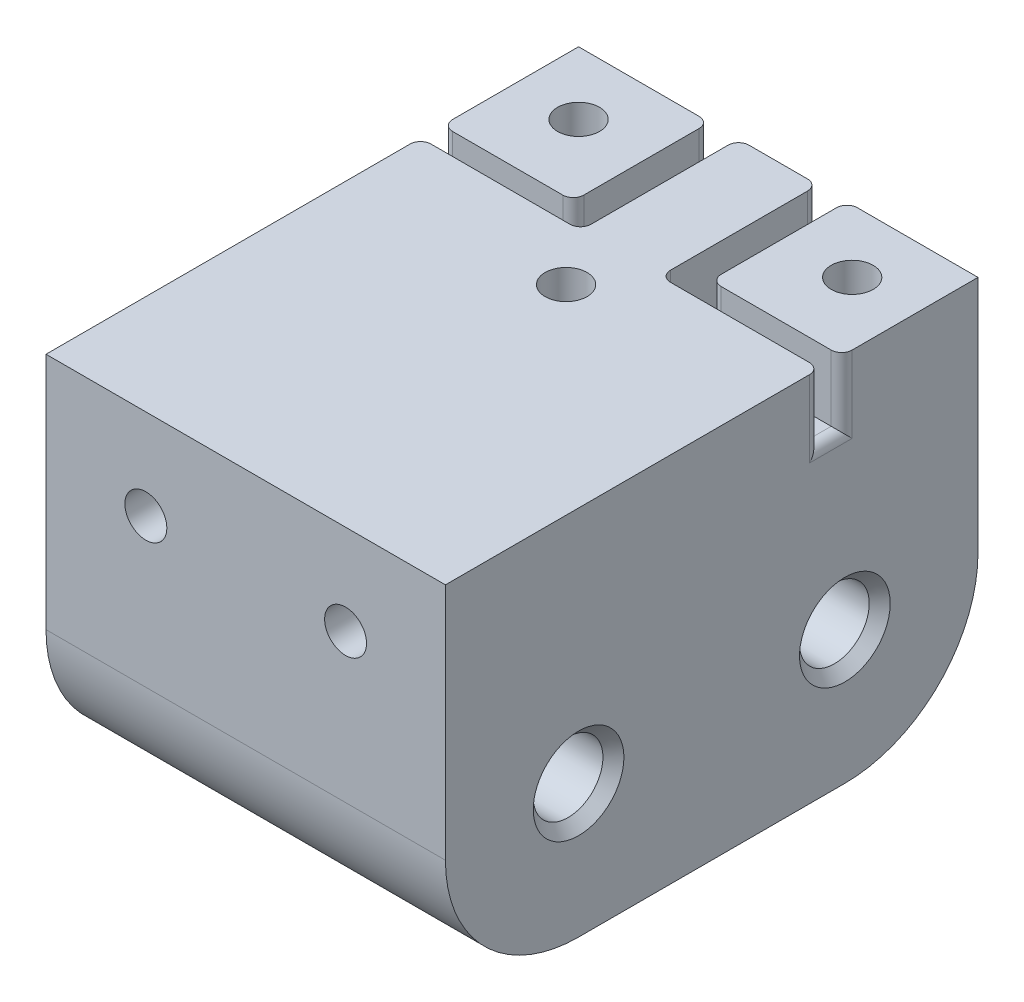
SolidWorks part; units mm, degrees
ref_plane "Front Plane" through (0, 0, 0) normal (0, 0, 1) x (1, 0, 0)
ref_plane "Top Plane" through (0, 0, 0) normal (0, 1, 0) x (1, 0, 0)
ref_plane "Right Plane" through (0, 0, 0) normal (1, 0, 0) x (0, 0, -1)
sketch "Sketch1" plane through (0, 0, 0) normal (1, 0, 0) x (0, 0, -1)
  line L0 (25.4, 22.75) -> (25.4, 0) construction
  line L1 (0, 22.75) -> (50.8, 22.75)
  line L2 (0, 22.75) -> (0, 0)
  line L3 (0, 0) -> (50.8, 0)
  line L4 (50.8, 22.75) -> (50.8, 0)
  circle A0 centre (12.7, 0) radius 3.325
  circle A1 centre (38.1, 0) radius 3.325
  circle A2 centre (12.7, 0) radius 12.7
  circle A3 centre (38.1, 0) radius 12.7
  dimension "D1" = 6.65
  dimension "D6" = 25.4
  dimension "D2" = 25.4
  dimension "D3" = 50.8
  dimension "D4" = 12.7
  dimension "D5" = 22.75
extrude "Boss-Extrude2" add sketch "Sketch1" along normal blind 38.1 contours L3 A2 A0 | L3 A2 A0 | L3 A3 A1 | L3 A3 A1 | L1 L0 L3 A3 L4 | L0 L1 L2 L3 A2 region at (0, 16.0478, -38.1) region at (0, 16.0478, -12.7) region at (0, -5.6828, -12.7) region at (0, 5.6828, -38.1) region at (0, 5.6828, -12.7) region at (0, -5.6828, -38.1)
ref_plane "Plane1" through (0, -12.7, 0) normal (0, -1, 0) x (-1, 0, 0)
sketch "Sketch6" plane through (0, -12.7, 0) normal (0, -1, 0) x (-1, 0, 0)
  line L0 (-38.1, 38.1) -> (0, 38.1)
  line L1 (-38.1, 50.8) -> (-38.1, 25.4) construction
  line L2 (0, 25.4) -> (0, 50.8) construction
  line L3 (-38.1, 12.7) -> (0, 12.7)
  line L4 (-38.1, 25.4) -> (-38.1, 0) construction
  line L5 (0, 0) -> (0, 25.4) construction
  line L7 (-38.1, 38.1) -> (0, 38.1)
  line L8 (-38.1, 38.1) -> (-38.1, 12.7)
  line L9 (-38.1, 12.7) -> (0, 12.7)
  line L10 (0, 38.1) -> (0, 12.7)
  circle A0 centre (-19.05, 38.1) radius 2
  circle A1 centre (-19.05, 12.7) radius 2
  dimension "D1" = 4
extrude "Cut-Extrude5" cut sketch "Sketch6" against normal up to next contours A0 | A1
extrude "Boss-Extrude3" add sketch "Sketch6<3>" against normal up to next contours A1 L3 L10 L0 A0 L8 region at (19.05, -12.7, -25.4)
sketch "Sketch6<3>" plane through (0, -12.7, 0) normal (0, -1, 0) x (-1, 0, 0) same geometry as "Sketch6"
sketch "Sketch10" plane through (0, 0, 0) normal (0, 0, 1) x (1, 0, 0)
  line L0 (38.1, 22.75) -> (38.1, 0) construction
  line L1 (0, 22.75) -> (38.1, 22.75)
  line L2 (0, 22.75) -> (0, 5.5563)
  line L3 (0, 5.5563) -> (38.1, 5.5563)
  line L4 (38.1, 22.75) -> (38.1, 5.5563)
  line L5 (19.05, 22.75) -> (19.05, 5.5563) construction
  line L6 (0, 14.1531) -> (19.05, 14.1531) construction
  line L7 (19.05, 14.1531) -> (38.1, 14.1531) construction
  circle A0 centre (9.525, 14.1531) radius 2
  circle A1 centre (28.575, 14.1531) radius 2
  dimension "D2" = 4
  dimension "D1" = 17.1937
extrude "Cut-Extrude6" cut sketch "Sketch10" against normal blind 8 contours A0 | A1 region at (9.525, 14.1531, 0) region at (28.575, 14.1531, 0)
chamfer "Chamfer1" distance 1 angle 45 4 edges at (38.1, 0, -16.025) (38.1, 0, -41.425) (0, 0, -16.025) (0, 0, -41.425)
sketch "Sketch15" plane through (0, 22.75, 0) normal (0, 1, 0) x (1, 0, 0)
  line L0 (0, 50.8) -> (38.1, 50.8) construction
  line L5 (0, 37.795) -> (12.5, 37.795)
  line L6 (12.5, 37.795) -> (12.5, 50.8)
  line L8 (15.26, 50.8) -> (15.26, 35.725)
  line L9 (15.26, 35.725) -> (0, 35.725)
  line L11 (0, 36.76) -> (15.26, 36.76) construction
  line L12 (19.05, 25.4) -> (19.05, 50.8) construction
  line L13 (13.88, 50.8) -> (13.88, 35.725) construction
  line L14 (22.84, 35.725) -> (38.1, 35.725)
  line L15 (22.84, 50.8) -> (22.84, 35.725)
  line L17 (25.6, 37.795) -> (25.6, 50.8)
  line L18 (38.1, 37.795) -> (25.6, 37.795)
  line L20 (0, 50.8) -> (38.1, 50.8)
  line L21 (0, 50.8) -> (0, 25.4)
  line L22 (0, 25.4) -> (38.1, 25.4)
  line L23 (38.1, 50.8) -> (38.1, 25.4)
  line L25 (0, 35.725) -> (0, 25.4) construction
  line M70 (0, 50.8) -> (0, 0)
  line M72 (38.1, 0) -> (38.1, 50.8)
  line M73 (38.1, 50.8) -> (0, 50.8)
  dimension "D1" = 25.4
  dimension "D2" = 2.07
  dimension "D6" = 11.36
  dimension "D3" = 2.76
  dimension "D4" = 15.26
  dimension "D5" = 12.5
  dimension "D7" = 38.1
extrude "Cut-Extrude9" cut sketch "Sketch15" against normal blind 6.3 contours L9 L8 L6 L5 M73 M70 | L18 L17 L15 L14 M72 M73 region at (6.25, 22.75, -37.5805) region at (24.22, 22.75, -50.5855)
fillet "Fillet3" radius 1 16 edges at (25.6, 19.6, -37.795) (22.84, 19.6, -35.725) (15.26, 19.6, -35.725) (12.5, 19.6, -37.795) (38.1, 19.6, -35.725) (38.1, 16.45, -36.76) (38.1, 19.6, -37.795) (25.6, 19.6, -50.8) (24.22, 16.45, -50.8) (22.84, 19.6, -50.8) (15.26, 19.6, -50.8) (13.88, 16.45, -50.8) (12.5, 19.6, -50.8) (0, 19.6, -37.795) (0, 16.45, -36.76) (0, 19.6, -35.725)
sketch "Sketch16" plane through (0, 22.75, 0) normal (0, 1, 0) x (1, 0, 0)
  line L0 (19.05, 50.8) -> (19.05, 25.4) construction
  line L1 (0, 50.8) -> (38.1, 50.8)
  line L2 (0, 50.8) -> (0, 25.4)
  line L3 (0, 25.4) -> (38.1, 25.4)
  line L4 (38.1, 50.8) -> (38.1, 25.4)
  circle A0 centre (19.05, 30.56) radius 2
  circle A1 centre (6, 44.8) radius 2
  circle A2 centre (32.1, 44.8) radius 2
  dimension "D6" = 4
  dimension "D1" = 25.4
  dimension "D2" = 38.1
  dimension "D3" = 5.16
  dimension "D4" = 6
  dimension "D5" = 6
extrude "Cut-Extrude10" cut sketch "Sketch16" against normal blind 5 contours A2 | L0 A0 | A0 L0 | A1 region at (19.8988, 22.75, -30.56) region at (18.2012, 22.75, -30.56) region at (32.1, 22.75, -44.8)
equation "\"Ø Smaller Shaft\"=6.35"
equation "\"Shaft Distance\"= 25.4"
equation "\"Width\"= \"Ø Smaller Shaft\" * 2 + \"Shaft Distance\" + \"Width End\" * 2"
equation "\"Width End\"= 6.35"
equation "\"Length\"= 38.1"
equation "\"Rod to Belt\"= 31.75 + 3"
equation "\"Nom Tolerance\"= 0.15"
equation "\"D1@Sketch1\"=\"Ø Smaller Shaft\" + \"Nom Tolerance\"*2"
equation "\"D2@Sketch1\"=\"Shaft Distance\""
equation "\"D3@Sketch1\"= \"Width\""
equation "\"D4@Sketch1\"=\"Shaft Distance\"/2"
equation "\"Belt\"= 6"
equation "\"Belt Thickness\"=1.38"
equation "\"Ø Pulley\"= 10.9"
equation "\"Pully Distance\"= 35"
equation "\"D6@Sketch1\"=\"Ø Smaller Shaft\"*4"
equation "\"D5@Sketch1\"=\"Rod to Belt\"+(\"Belt\"/2)-15"
equation "\"D1@Boss-Extrude2\"=\"Length\""
equation "\"Ø Outer Washer\"=12.7"
equation "\"Washer Thickness\"=2"
equation "\"D1\"= \"Washer Thickness\""
equation "\"M3 Heated Insert Hole\"= 4"
equation "\"D1@Sketch6\"=\"M3 Heated Insert Hole\""
equation "\"D1@Sketch10\"=\"Rod to Belt\"+(\"Belt\"/2)-15-(\"Ø Smaller Shaft\"*1.75)/2"
equation "\"D2@Sketch10\"=\"M3 Heated Insert Hole\""
equation "\"Ø Graphite Holder\"= 17"
